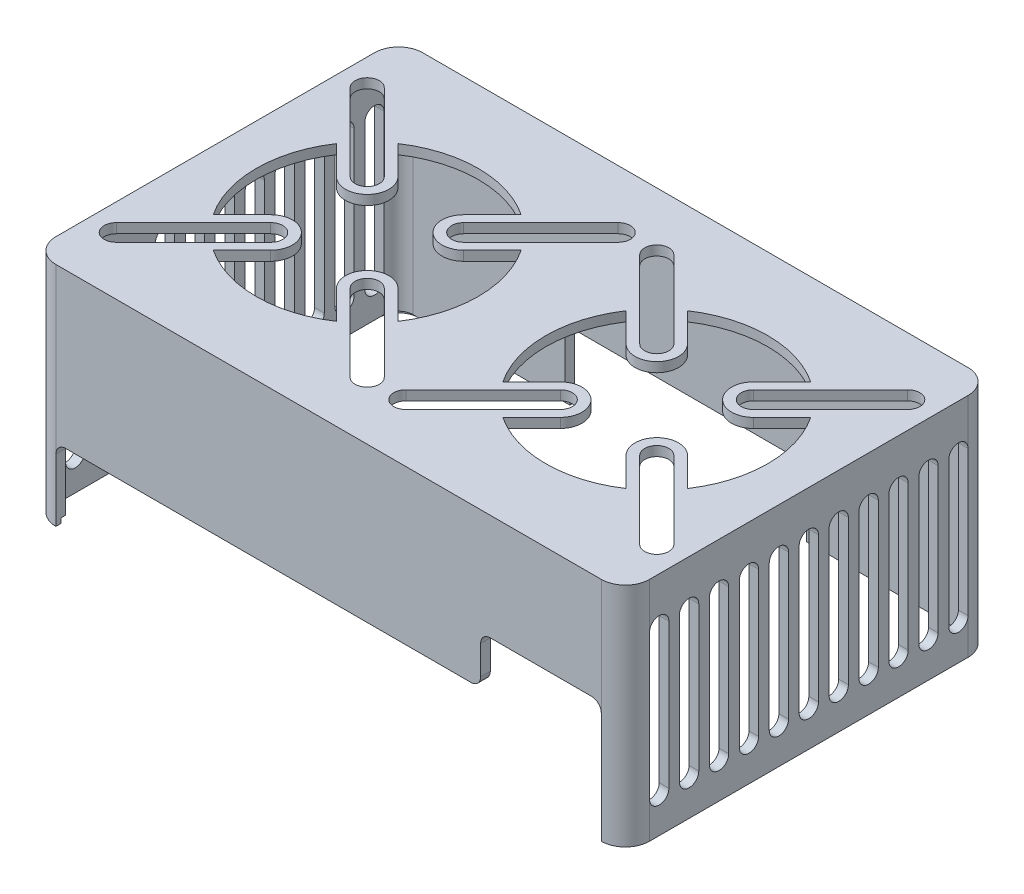
SolidWorks part; units mm, degrees
material "ABS"
ref_plane "Front Plane" through (0, 0, 0) normal (0, 0, 1) x (1, 0, 0)
ref_plane "Top Plane" through (0, 0, 0) normal (0, 1, 0) x (1, 0, 0)
ref_plane "Right Plane" through (0, 0, 0) normal (1, 0, 0) x (0, 0, -1)
sketch "Sketch1" plane through (0, 0, 0) normal (0, 1, 0) x (1, 0, 0)
  line L0 (-59.5, -33) -> (-59.5, 33)
  line L1 (-56.5, -33) -> (56.5, -33) construction
  line L2 (-56.5, -33) -> (-56.5, 33) construction
  line L3 (-56.5, 33) -> (56.5, 33) construction
  line L4 (56.5, -33) -> (56.5, 33) construction
  line L5 (-56.5, -33) -> (56.5, 33) construction
  line L6 (-56.5, 33) -> (56.5, -33) construction
  line L7 (-56.5, -38) -> (56.5, -38)
  line L8 (-61.5, -33) -> (-61.5, 33)
  line L9 (-56.5, 38) -> (56.5, 38)
  line L10 (61.5, -33) -> (61.5, 33)
  line L11 (-61.5, -38) -> (61.5, 38) construction
  line L12 (-61.5, 38) -> (61.5, -38) construction
  line L13 (-56.5, 36) -> (56.5, 36)
  line L14 (59.5, -33) -> (59.5, 33)
  line L15 (-56.5, -36) -> (56.5, -36)
  arc A0 (56.5, -38) -> (61.5, -33) centre (56.5, -33) ccw
  arc A1 (-61.5, 33) -> (-56.5, 38) centre (-56.5, 33) cw
  arc A2 (-56.5, -38) -> (-61.5, -33) centre (-56.5, -33) cw
  arc A3 (56.5, 38) -> (61.5, 33) centre (56.5, 33) cw
  arc A4 (-59.5, 33) -> (-56.5, 36) centre (-56.5, 33) cw
  arc A5 (56.5, 36) -> (59.5, 33) centre (56.5, 33) cw
  arc A6 (56.5, -36) -> (59.5, -33) centre (56.5, -33) ccw
  arc A7 (-56.5, -36) -> (-59.5, -33) centre (-56.5, -33) cw
  point P0 (0, 0)
  point P5 (0, 0)
  dimension "D5" = 5
  dimension "D1" = 66
  dimension "D2" = 113
  dimension "D3" = 5
  dimension "D4" = 5
  dimension "D6" = 2
extrude "Boss-Extrude1" add sketch "Sketch1" along normal blind 45
sketch "Sketch2" plane through (0, 45, 0) normal (0, 1, 0) x (1, 0, 0)
  line L4 (-59.5, 33) -> (-59.5, -33) construction
  line L5 (-56.5, -36) -> (56.5, -36) construction
  line L6 (59.5, -33) -> (59.5, 33) construction
  line L7 (56.5, 36) -> (-56.5, 36) construction
  line L8 (-56.5, -37) -> (56.5, -37)
  line L9 (60.5, -33) -> (60.5, 33)
  line L10 (56.5, 37) -> (-56.5, 37)
  line L11 (-60.5, 33) -> (-60.5, -33)
  line L12 (-56.5, -37) -> (56.5, -37)
  line L13 (60.5, -33) -> (60.5, 33)
  line L14 (56.5, 37) -> (-56.5, 37)
  line L15 (-60.5, 33) -> (-60.5, -33)
  line L16 (-59.5, 33) -> (-59.5, -33)
  line L17 (-56.5, -36) -> (56.5, -36)
  line L18 (59.5, -33) -> (59.5, 33)
  line L19 (56.5, 36) -> (-56.5, 36)
  arc A4 (-56.5, 36) -> (-59.5, 33) centre (-56.5, 33) ccw construction
  arc A5 (-59.5, -33) -> (-56.5, -36) centre (-56.5, -33) ccw construction
  arc A6 (56.5, -36) -> (59.5, -33) centre (56.5, -33) ccw construction
  arc A7 (59.5, 33) -> (56.5, 36) centre (56.5, 33) ccw construction
  arc A8 (-60.5, -33) -> (-56.5, -37) centre (-56.5, -33) ccw
  arc A9 (56.5, -37) -> (60.5, -33) centre (56.5, -33) ccw
  arc A10 (60.5, 33) -> (56.5, 37) centre (56.5, 33) ccw
  arc A11 (-56.5, 37) -> (-60.5, 33) centre (-56.5, 33) ccw
  arc A12 (-60.5, -33) -> (-56.5, -37) centre (-56.5, -33) ccw
  arc A13 (56.5, -37) -> (60.5, -33) centre (56.5, -33) ccw
  arc A14 (60.5, 33) -> (56.5, 37) centre (56.5, 33) ccw
  arc A15 (-56.5, 37) -> (-60.5, 33) centre (-56.5, 33) ccw
  arc A16 (-56.5, 36) -> (-59.5, 33) centre (-56.5, 33) ccw
  arc A17 (-59.5, -33) -> (-56.5, -36) centre (-56.5, -33) ccw
  arc A18 (56.5, -36) -> (59.5, -33) centre (56.5, -33) ccw
  arc A19 (59.5, 33) -> (56.5, 36) centre (56.5, 33) ccw
  dimension "D1" = 1
extrude "Cut-Extrude2" cut sketch "Sketch2" along normal blind 1 from surface starting at face at (0, 0, 0)
sketch "Sketch3" plane through (0, 0, -38) normal (0, 0, -1) x (-1, 0, 0)
  line L0 (-56.5, 0) -> (56.5, 0) construction
  line L1 (-25, 0) -> (25, 0)
  line L2 (-25, 0) -> (-25, 15)
  line L3 (-25, 15) -> (25, 15)
  line L4 (25, 0) -> (25, 15)
  point P6 (0, 0)
  dimension "D1" = 15
  dimension "D2" = 50
extrude "Cut-Extrude3" cut sketch "Sketch3" against normal up to surface (2 mm away) up to face at (0, 23, -36)
sketch "Sketch4" plane through (0, 0, 38) normal (0, 0, 1) x (1, 0, 0)
  line L0 (-56.5, 0) -> (56.5, 0) construction
  line L1 (-56.5, 0) -> (56.5, 0)
  line L2 (-56.5, 0) -> (-56.5, 15)
  line L3 (-56.5, 15) -> (56.5, 15)
  line L4 (56.5, 0) -> (56.5, 15)
  line L5 (-56.5, 45) -> (-56.5, 0) construction
  point P6 (0, 0)
  dimension "D1" = 15
extrude "Cut-Extrude4" cut sketch "Sketch4" against normal up to surface (2 mm away) up to face at (0, 23, 36)
sketch "Sketch5" plane through (-61.5, 0, 0) normal (-1, 0, 0) x (0, 0, 1)
  line L0 (-31, 37.5) -> (-31, 7.5) construction
  line L1 (-29, 37.5) -> (-29, 7.5)
  line L2 (-33, 37.5) -> (-33, 7.5)
  line L4 (33, 45) -> (33, 0) construction
  line L5 (-33, 45) -> (-33, 0) construction
  arc A0 (-29, 37.5) -> (-33, 37.5) centre (-31, 37.5) ccw
  arc A1 (-33, 7.5) -> (-29, 7.5) centre (-31, 7.5) ccw
  point P2 (-31, 22.5)
  point P9 (33, 22.5)
  dimension "D1" = 2
  dimension "D2" = 30
  dimension "D3" = 2
extrude "Cut-Extrude6" cut sketch "Sketch5" against normal through all both and the other way through all
pattern_linear "LPattern2" count 11 spacing 6.2 along (0, 0, 1) of "Cut-Extrude6"
sketch "Sketch6" plane through (0, 45, 0) normal (0, 1, 0) x (1, 0, 0)
  line L0 (-56.5, -38) -> (56.5, -38) construction
  line L1 (61.5, -33) -> (61.5, 33) construction
  line L2 (56.5, 38) -> (-56.5, 38) construction
  line L3 (-61.5, 33) -> (-61.5, -33) construction
  line L4 (-56.5, -38) -> (56.5, -38)
  line L5 (61.5, -33) -> (61.5, 33)
  line L6 (56.5, 38) -> (-56.5, 38)
  line L7 (-61.5, 33) -> (-61.5, -33)
  arc A0 (-61.5, -33) -> (-56.5, -38) centre (-56.5, -33) ccw construction
  arc A1 (56.5, -38) -> (61.5, -33) centre (56.5, -33) ccw construction
  arc A2 (61.5, 33) -> (56.5, 38) centre (56.5, 33) ccw construction
  arc A3 (-56.5, 38) -> (-61.5, 33) centre (-56.5, 33) ccw construction
  arc A4 (-61.5, -33) -> (-56.5, -38) centre (-56.5, -33) ccw
  arc A5 (56.5, -38) -> (61.5, -33) centre (56.5, -33) ccw
  arc A6 (61.5, 33) -> (56.5, 38) centre (56.5, 33) ccw
  arc A7 (-56.5, 38) -> (-61.5, 33) centre (-56.5, 33) ccw
extrude "Boss-Extrude2" add sketch "Sketch6" along normal blind 2
sketch "Sketch7" plane through (0, 47, 0) normal (0, 1, 0) x (1, 0, 0)
  line L0 (-23.5912, 0) -> (34.7191, 0) construction
  line L1 (-55, 25) -> (-5, 25) construction
  line L2 (-55, 25) -> (-55, -25) construction
  line L3 (-55, -25) -> (-5, -25) construction
  line L4 (-5, 25) -> (-5, -25) construction
  line L5 (5, 25) -> (55, 25) construction
  line L6 (5, 25) -> (5, -25) construction
  line L7 (5, -25) -> (55, -25) construction
  line L8 (55, 25) -> (55, -25) construction
  line L9 (-30, 25) -> (-30, -25) construction
  line L10 (30, 25) -> (30, -25) construction
  line L11 (-56, 26) -> (-40, 10) construction
  line L12 (-54.2322, 27.7678) -> (-38.2322, 11.7678)
  line L13 (-57.7678, 24.2322) -> (-41.7678, 8.2322)
  line L14 (56.5, 38) -> (-56.5, 38) construction
  line L15 (-52.818, 29.182) -> (-36.818, 13.182)
  line L16 (-59.182, 22.818) -> (-43.182, 6.818)
  line L17 (-4, 26) -> (-20, 10) construction
  line L18 (-5.7678, 27.7678) -> (-21.7678, 11.7678)
  line L19 (-2.2322, 24.2322) -> (-18.2322, 8.2322)
  line L20 (-0.818, 22.818) -> (-16.818, 6.818)
  line L21 (-7.182, 29.182) -> (-23.182, 13.182)
  line L22 (0, 0) -> (0, -24.1699) construction
  line L23 (-56, -26) -> (-40, -10) construction
  line L24 (-54.2322, -27.7678) -> (-38.2322, -11.7678)
  line L25 (-57.7678, -24.2322) -> (-41.7678, -8.2322)
  line L26 (-4, -26) -> (-20, -10) construction
  line L27 (-5.7678, -27.7678) -> (-21.7678, -11.7678)
  line L28 (-2.2322, -24.2322) -> (-18.2322, -8.2322)
  line L29 (-7.182, -29.182) -> (-23.182, -13.182)
  line L30 (-0.818, -22.818) -> (-16.818, -6.818)
  line L31 (-59.182, -22.818) -> (-43.182, -6.818)
  line L32 (-52.818, -29.182) -> (-36.818, -13.182)
  line L33 (56, -26) -> (40, -10) construction
  line L34 (54.2322, -27.7678) -> (38.2322, -11.7678)
  line L35 (57.7678, -24.2322) -> (41.7678, -8.2322)
  line L36 (4, -26) -> (20, -10) construction
  line L37 (5.7678, -27.7678) -> (21.7678, -11.7678)
  line L38 (2.2322, -24.2322) -> (18.2322, -8.2322)
  line L39 (4, 26) -> (20, 10) construction
  line L40 (5.7678, 27.7678) -> (21.7678, 11.7678)
  line L41 (2.2322, 24.2322) -> (18.2322, 8.2322)
  line L42 (56, 26) -> (40, 10) construction
  line L43 (54.2322, 27.7678) -> (38.2322, 11.7678)
  line L44 (57.7678, 24.2322) -> (41.7678, 8.2322)
  line L45 (59.182, 22.818) -> (43.182, 6.818)
  line L46 (52.818, 29.182) -> (36.818, 13.182)
  line L47 (7.182, 29.182) -> (23.182, 13.182)
  line L48 (0.818, 22.818) -> (16.818, 6.818)
  line L49 (0.818, -22.818) -> (16.818, -6.818)
  line L50 (7.182, -29.182) -> (23.182, -13.182)
  line L51 (52.818, -29.182) -> (36.818, -13.182)
  line L52 (59.182, -22.818) -> (43.182, -6.818)
  circle A9 centre (-30, 0) radius 23
  circle A10 centre (30, 0) radius 23
  arc A11 (-54.2322, 27.7678) -> (-57.7678, 24.2322) centre (-56, 26) ccw
  arc A12 (-41.7678, 8.2322) -> (-38.2322, 11.7678) centre (-40, 10) ccw
  arc A13 (-43.182, 6.818) -> (-36.818, 13.182) centre (-40, 10) ccw
  arc A14 (-52.818, 29.182) -> (-59.182, 22.818) centre (-56, 26) ccw
  arc A15 (-5.7678, 27.7678) -> (-2.2322, 24.2322) centre (-4, 26) cw
  arc A16 (-18.2322, 8.2322) -> (-21.7678, 11.7678) centre (-20, 10) cw
  arc A17 (-7.182, 29.182) -> (-0.818, 22.818) centre (-4, 26) cw
  arc A18 (-16.818, 6.818) -> (-23.182, 13.182) centre (-20, 10) cw
  arc A19 (-54.2322, -27.7678) -> (-57.7678, -24.2322) centre (-56, -26) cw
  arc A20 (-41.7678, -8.2322) -> (-38.2322, -11.7678) centre (-40, -10) cw
  arc A21 (-5.7678, -27.7678) -> (-2.2322, -24.2322) centre (-4, -26) ccw
  arc A22 (-18.2322, -8.2322) -> (-21.7678, -11.7678) centre (-20, -10) ccw
  arc A23 (-16.818, -6.818) -> (-23.182, -13.182) centre (-20, -10) ccw
  arc A24 (-7.182, -29.182) -> (-0.818, -22.818) centre (-4, -26) ccw
  arc A25 (-52.818, -29.182) -> (-59.182, -22.818) centre (-56, -26) cw
  arc A26 (-43.182, -6.818) -> (-36.818, -13.182) centre (-40, -10) cw
  arc A27 (54.2322, -27.7678) -> (57.7678, -24.2322) centre (56, -26) ccw
  arc A28 (41.7678, -8.2322) -> (38.2322, -11.7678) centre (40, -10) ccw
  arc A29 (5.7678, -27.7678) -> (2.2322, -24.2322) centre (4, -26) cw
  arc A30 (18.2322, -8.2322) -> (21.7678, -11.7678) centre (20, -10) cw
  arc A31 (5.7678, 27.7678) -> (2.2322, 24.2322) centre (4, 26) ccw
  arc A32 (18.2322, 8.2322) -> (21.7678, 11.7678) centre (20, 10) ccw
  arc A33 (54.2322, 27.7678) -> (57.7678, 24.2322) centre (56, 26) cw
  arc A34 (41.7678, 8.2322) -> (38.2322, 11.7678) centre (40, 10) cw
  arc A35 (52.818, 29.182) -> (59.182, 22.818) centre (56, 26) cw
  arc A36 (43.182, 6.818) -> (36.818, 13.182) centre (40, 10) cw
  arc A37 (16.818, 6.818) -> (23.182, 13.182) centre (20, 10) ccw
  arc A38 (7.182, 29.182) -> (0.818, 22.818) centre (4, 26) ccw
  arc A39 (7.182, -29.182) -> (0.818, -22.818) centre (4, -26) cw
  arc A40 (16.818, -6.818) -> (23.182, -13.182) centre (20, -10) cw
  arc A41 (43.182, -6.818) -> (36.818, -13.182) centre (40, -10) ccw
  arc A42 (52.818, -29.182) -> (59.182, -22.818) centre (56, -26) ccw
  point P17 (-48, 18)
  point P38 (-12, 18)
  point P51 (-48, -18)
  point P58 (-12, -18)
  point P77 (48, -18)
  point P84 (12, -18)
  point P91 (12, 18)
  point P98 (48, 18)
  dimension "D6" = 2.5
  dimension "D9" = 10
  dimension "D10" = 46
  dimension "D12" = 46
  dimension "D1" = 50
  dimension "D2" = 50
  dimension "D3" = 50
  dimension "D4" = 5
  dimension "D5" = 5
  dimension "D7" = 45
  dimension "D8" = 1
  dimension "D11" = 2
extrude "Cut-Extrude7" cut sketch "Sketch7" against normal through all contours L31 A26 L32 A9 L29 A23 L30 L20 A18 L21 L15 A13 L16 | A20 L25 A9 L24 | A19 L24 A9 L25 | L27 A21 L28 A9 | L28 A22 L27 A9 | A16 L19 A9 L18 | A15 L18 A9 L19 | L12 A11 L13 A9 | L13 A12 L12 A9 | L40 A31 L41 A10 | L41 A32 L40 A10 | A30 L38 A10 L37 | A29 L37 A10 L38 | L35 A28 L34 A10 | L34 A27 L35 A10 | A34 L44 A10 L43 | A33 L43 A10 L44 | A41 L52 A10 L45 A36 L46 L47 A37 L48 L49 A40 L50 L51 region at (-51.8168, 47, -21.8168) region at (-42.4113, 47, -12.4113) region at (-30, 47, 0) region at (-17.5887, 47, -12.4113) region at (-8.1832, 47, -21.8168) region at (-51.8168, 47, 21.8168) region at (-42.4113, 47, 12.4113) region at (30, 47, 0) region at (8.1832, 47, -21.8168) region at (17.5887, 47, -12.4113) region at (42.4113, 47, -12.4113) region at (51.8168, 47, -21.8168) region at (-17.5887, 47, 12.4113) region at (-8.1832, 47, 21.8168) region at (8.1832, 47, 21.8168) region at (17.5887, 47, 12.4113) region at (51.8168, 47, 21.8168) region at (42.4113, 47, 12.4113)
sketch "Sketch8" plane through (0, 0, 38) normal (0, 0, 1) x (1, 0, 0)
  line L1 (56.5, 15) -> (31.5, 15)
  line L2 (56.5, 15) -> (56.5, 25)
  line L3 (56.5, 25) -> (31.5, 25)
  line L4 (31.5, 15) -> (31.5, 25)
  dimension "D1" = 10
  dimension "D2" = 25
extrude "Cut-Extrude8" cut sketch "Sketch8" against normal up to surface (2 mm away) up to face at (0, 30, 36)
fillet "Fillet1" radius 2 1 edges at (31.5, 15, 37)
fillet "Fillet2" radius 2 1 edges at (31.5, 25, 37)
fillet "Fillet3" radius 2 2 edges at (-25, 15, -37) (25, 15, -37)
fillet "Fillet4" radius 2 2 edges at (56.5, 25, 37) (-56.5, 15, 37)
